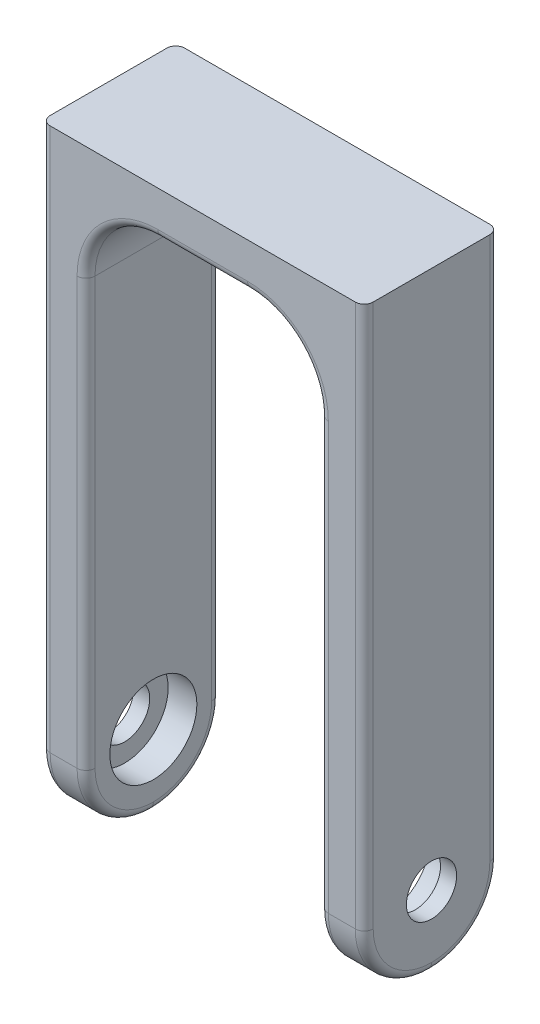
SolidWorks part; units mm, degrees
ref_plane "前视基准面" through (0, 0, 0) normal (0, 0, 1) x (1, 0, 0)
ref_plane "上视基准面" through (0, 0, 0) normal (0, 1, 0) x (1, 0, 0)
ref_plane "右视基准面" through (0, 0, 0) normal (1, 0, 0) x (0, 0, -1)
sketch "草图1" plane through (0, 0, 0) normal (0, 1, 0) x (1, 0, 0)
  line L1 (18, 7.5) -> (-18, 7.5)
  line L2 (18, 7.5) -> (18, -7.5)
  line L3 (18, -7.5) -> (-18, -7.5)
  line L4 (-18, 7.5) -> (-18, -7.5)
  line L5 (18, 7.5) -> (-18, -7.5) construction
  line L6 (18, -7.5) -> (-18, 7.5) construction
  point P0 (0, 0)
extrude "凸台-拉伸1" add sketch "草图1" against normal blind 68
sketch "草图3" plane through (0, 0, 7.5) normal (0, 0, 1) x (1, 0, 0)
  line L0 (-18, -68) -> (18, -68) construction
  line L1 (-13, -68) -> (13, -68)
  line L2 (-13, -68) -> (-13, -5)
  line L3 (-13, -5) -> (13, -5)
  line L4 (13, -68) -> (13, -5)
extrude "切除-拉伸1" cut sketch "草图3" against normal through all
fillet "圆角1" radius 8 2 edges at (13, -5, 0) (-13, -5, 0)
fillet "圆角3" radius 7.5 4 edges at (15.5, -68, -7.5) (15.5, -68, 7.5) (-15.5, -68, -7.5) (-15.5, -68, 7.5)
fillet "圆角2" radius 1 22 edges at (-18, -30.25, -7.5) (18, -30.25, -7.5) (18, -30.25, 7.5) (-18, -30.25, 7.5) (-10.6569, -7.3431, 7.5) (0, -5, 7.5) (10.6569, -7.3431, 7.5) (13, -36.75, 7.5) (13, -36.75, -7.5) (10.6569, -7.3431, -7.5) (0, -5, -7.5) (-10.6569, -7.3431, -7.5) (-13, -36.75, -7.5) (-13, -36.75, 7.5) (13, -65.8033, 5.3033) (13, -65.8033, -5.3033) (-13, -65.8033, -5.3033) (-13, -65.8033, 5.3033) (-18, -65.8033, 5.3033) (-18, -65.8033, -5.3033) (18, -65.8033, -5.3033) (18, -65.8033, 5.3033)
sketch "草图4" plane through (18, 0, 0) normal (1, 0, 0) x (0, 0, -1)
  circle A0 centre (0, -60) radius 2.8
extrude "切除-拉伸2" cut sketch "草图4" against normal through all
sketch "草图6" plane through (13, 0, 0) normal (1, 0, 0) x (0, 0, -1)
  circle A0 centre (0, -60) radius 4.85
extrude "切除-拉伸4" cut sketch "草图6" along normal blind 3.2
mirror "镜向1" about plane through (0, 0, 0) normal (1, 0, 0) of "切除-拉伸4"
fillet "圆角5" radius 13 rebuild error yes
